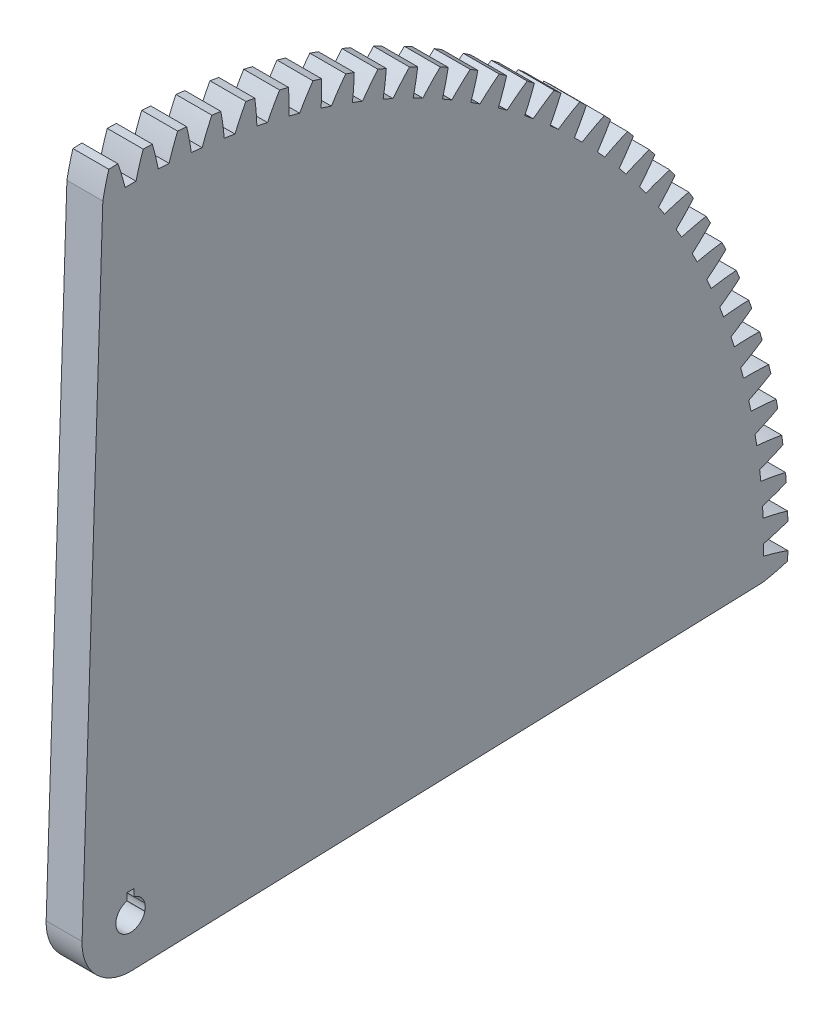
SolidWorks part; units mm, degrees
ref_plane "Plane1" through (0, 0, 0) normal (0, 0, 1) x (1, 0, 0)
ref_plane "Plane2" through (0, 0, 0) normal (0, 1, 0) x (1, 0, 0)
ref_plane "Plane3" through (0, 0, 0) normal (1, 0, 0) x (0, 0, -1)
sketch "HoldingSke" plane through (0, 0, 0) normal (0, 1, 0) x (1, 0, 0)
  line L0 (0, 0) -> (-0.1667, -0.2887)
  line L1 (-15, 0) -> (100, 0) construction
  line L2 (0, 0) -> (-2.1039, 2.3779)
  line L3 (0, 0) -> (-11.863, 4.5341)
  line L4 (0, 0) -> (-4.318, 7.479)
  line L5 (0, 0) -> (-46.8476, -17.4728)
  line L6 (0, 0) -> (-8.2896, -5.593)
  line L7 (-2.1039, 2.3779) -> (8.6586, 51.2059)
  line L8 (-76.2, 54.61) -> (-75.2, 54.61)
  line L9 (-67.7845, 28.3722) -> (-49.3413, 33.142)
  line L10 (-76.2, 71.12) -> (104.1128, 71.12)
  line L11 (0, 0) -> (-10, 0)
  line L12 (-76.2, 101.6) -> (-76.093, 101.6)
  line L13 (24.9733, 27.94) -> (52.9518, 28.4284)
  line L14 (24.9733, 27.94) -> (24.9743, 27.94)
  line L15 (24.9733, 27.94) -> (100.4006, 29.5858)
  line L16 (-63.627, -3) -> (-12.827, -3)
  circle A0 centre (0, 0) radius 3
  circle A1 centre (0, 0) radius 37.5
  circle A2 centre (0, 0) radius 37.5
  circle A3 centre (0, 0) radius 3
  dimension "MHD" = 75
  dimension "Hub_dia" = 75
  dimension "Bore" = 6
  dimension "MBD" = 6
  dimension "Num_teeth" = 120
  dimension "Pitch_radius" = 180.3128
  dimension "Pitch" = 0.3333
  dimension "Width" = 10
  dimension "Overall_len" = 50
  dimension "Show_teeth" = 120
  dimension "Thickness" = 10
  dimension "OAL" = 50.0001
  dimension "T_dim" = 1
  dimension "Ap" = 14.5
  dimension "H" = 19.05
  dimension "Backlash" = 0.107
  dimension "Addendum_fac" = 1
  dimension "Dedendum_fac" = 1.25
  dimension "Clearance_fac" = 0.25
  dimension "Dedendum_add" = 0.001
  dimension "Module" = 3
sketch "BasProSke" plane through (0, 0, 0) normal (0, 1, 0) x (1, 0, 0)
  line L0 (-10, 0) -> (60, 0) construction
  line L1 (0, 0) -> (0, 183)
  line L2 (0, 0) -> (10, 0)
  line L3 (10, 0) -> (10, 183)
  line L4 (10, 183) -> (0, 183)
  dimension "Diameter" = 366
  dimension "Thickness" = 10
revolve "Base-Revolve" add sketch "BasProSke" angle 360 about L0
sketch "TooCutSke" plane through (0, 0, 0) normal (1, 0, 0) x (0, 0, -1)
  line L1 (0, 0) -> (0, 107) construction
  line L2 (0, 0) -> (-2.5434, 179.982) construction
  line L3 (0, 0) -> (-9.423, 359.8505) construction
  line L4 (-2.5434, 179.982) -> (-4.7115, 179.9253) construction
  arc A0 (1.5113, 176.2425) -> (-1.5113, 176.2425) centre (0, 0) ccw
  arc A1 (3.5347, 182.9913) -> (-3.5347, 182.9913) centre (0, 0) ccw
  circle A2 centre (0, 0) radius 180 construction
  circle A3 centre (0, 0) radius 174.2666 construction
  arc A4 (-1.5113, 176.2425) -> (-3.5347, 182.9913) centre (-71.4076, 158.9648) ccw
  arc A5 (3.5347, 182.9913) -> (1.5113, 176.2425) centre (71.4076, 158.9648) ccw
  dimension "Root_dia" = 352.498
  dimension "Overcut_dia" = 366.0508
  dimension "Pitch_dia" = 360
  dimension "Base_dia" = 348.5332
  dimension "Flank_rad" = 72
  dimension "Half_ang" = 1.5
  dimension "Half_CT" = 2.1689
extrude "ToothCut" cut sketch "TooCutSke" along normal through all
fillet "Breaks" [suppressed] radius 0.06
fillet "RootFillets" [suppressed] radius 0.751
pattern_circular "TeethCuts" count 120 every 3 about axis through (-10, 0, 0) along (1, 0, 0) of "ToothCut", "RootFillets", "Breaks"
sketch "HubNeaOneSke" [suppressed] plane through (0, 0, 0) normal (-1, 0, 0) x (0, 0, 1)
  circle A0 centre (0, 0) radius 12.499
  dimension "Diameter" = 75
extrude "HubNearOne" [suppressed] add sketch "HubNeaOneSke" along normal blind 40.0001
sketch "HubNeaBotSke" [suppressed] plane through (0, 0, 0) normal (-1, 0, 0) x (0, 0, 1)
  circle A0 centre (0, 0) radius 12.7
  dimension "Diameter" = 75
extrude "HubNearBoth" [suppressed] add sketch "HubNeaBotSke" along normal blind 20
ref_plane "FarPln" through (10, 0, 0) normal (1, 0, 0) x (0, 0, -1)
sketch "HubFarSke" [suppressed] plane through (12.7, 0, 0) normal (1, 0, 0) x (0, 0, -1)
  circle A0 centre (0, 0) radius 12.7
  dimension "Diameter" = 75
extrude "HubFar" [suppressed] add sketch "HubFarSke" along normal blind 20
sketch "BorSke" plane through (0, 0, 0) normal (1, 0, 0) x (0, 0, -1)
  circle A0 centre (0, 0) radius 3
  dimension "Diameter" = 6
extrude "Bore" cut sketch "BorSke" along normal mid plane 100.0001
sketch "KeySke" plane through (0, 0, 0) normal (1, 0, 0) x (0, 0, -1)
  line L0 (-1, 0) -> (-1, 4)
  line L1 (-1, 4) -> (1, 4)
  line L2 (1, 4) -> (1, 0)
  line L3 (0, 0) -> (0, 34) construction
  line L4 (-1, 0) -> (1, 0)
  dimension "Offset" = 4
  dimension "Width" = 2
extrude "Keyway" cut sketch "KeySke" along normal mid plane 100.0001
pattern_circular "Keyway2" count 2 every 90 about axis through (0, 0, 0) along (1, 0, 0) of "Keyway"
sketch "Sketch1" plane through (10, 0, 0) normal (1, 0, 0) x (0, 0, -1)
  line L0 (0, 224.3134) -> (0, 0) construction
  line L1 (0, 0) -> (213.6921, 0) construction
  line L2 (176.0801, -7.7145) -> (0.4439, -13.4927)
  line L3 (-7.7145, 176.0801) -> (-13.4927, 0.4439)
  line L4 (176.0801, -7.7145) -> (186.3109, -8.4985)
  line L5 (186.3109, -8.4985) -> (187.8056, -54.5918)
  line L6 (187.8056, -54.5918) -> (141.6436, -161.7802)
  line L7 (141.6436, -161.7802) -> (0.4439, -208.078)
  line L8 (0.4439, -208.078) -> (-102.8323, -176.0574)
  line L9 (-102.8323, -176.0574) -> (-161.48, -112.2681)
  line L10 (-161.48, -112.2681) -> (-203.2321, -19.1491)
  line L11 (-203.2321, -19.1491) -> (-189.3957, 62.8481)
  line L12 (-189.3957, 62.8481) -> (-115.067, 184.8791)
  line L13 (-115.067, 184.8791) -> (-32.7498, 211.87)
  line L14 (-32.7498, 211.87) -> (-14.2518, 194.7007)
  line L15 (-14.2518, 194.7007) -> (-7.7145, 176.0801)
  arc A0 (-13.4927, 0.4439) -> (0.4439, -13.4927) centre (0, 0) ccw
  dimension "D1" = 27
extrude "Cut-Extrude1" cut sketch "Sketch1" against normal through all
sketch "Sketch2" plane through (10, 0, 0) normal (1, 0, 0) x (0, 0, -1)
  line L0 (-1, 3.9762) -> (-1, 6)
  line L1 (-1, 4) -> (-1, 2.8284) construction
  line L2 (-1, 6) -> (1, 6)
  line L3 (1, 6) -> (1, 3.9762)
  line L4 (1, 4) -> (-1, 4) construction
  arc A0 (-1, 3.9762) -> (1, 3.9762) centre (0, 0) ccw
  dimension "D1" = 8.2
  dimension "D2" = 2
extrude "Cut-Extrude2" cut sketch "Sketch2" against normal through all
equation "' \"Module@HoldingSke\" = 6.35"
equation "' \"Num_teeth@HoldingSke\" = 12"
equation "' \"Ap@HoldingSke\" =  20"
equation "' \"Width@HoldingSke\" = 0.5 * 25.4"
equation "' \"Hub_dia@HoldingSke\"= 1 * 25.4"
equation "' \"Overall_len@HoldingSke\" = 1.0 * 25.4"
equation "' \"Bore@HoldingSke\" = 0.75 * 25.4"
equation "' \"T_dim@HoldingSke\" = 0.1 * 25.4"
equation "' \"Width@KeySke\" = 0.25 * 25.4"
equation "' \"Show_teeth@HoldingSke\" = 13"
equation "' \"Backlash@HoldingSke\" = 0.009 * 25.4"
equation "' \"Addendum_fac@HoldingSke\" = 1.0"
equation "' \"Dedendum_fac@HoldingSke\" = 1.25"
equation "' \"Dedendum_add@HoldingSke\" = 0.00005 * 25.4"
equation "' \"Clearance_fac@HoldingSke\" = 0.25"
equation "\"Pitch@HoldingSke\" = 1 / \"Module@HoldingSke\""
equation "\"Overcut_dia@TooCutSke\" = (\"Num_teeth@HoldingSke\" + 2 * \"Addendum_fac@HoldingSke\") / \"Pitch@HoldingSke\" + 0.002 * 25.4"
equation "\"Pitch_dia@TooCutSke\" = \"Num_teeth@HoldingSke\" / \"Pitch@HoldingSke\""
equation "\"Base_dia@TooCutSke\" = \"Num_teeth@HoldingSke\" / \"Pitch@HoldingSke\" * cos((\"Ap@HoldingSke\"  * 3.14159265 / 180))"
equation "\"Root_dia@TooCutSke\" = (\"Num_teeth@HoldingSke\" + 2) / \"Pitch@HoldingSke\" - 2 * (\"Addendum_fac@HoldingSke\" + \"Dedendum_fac@HoldingSke\") / \"Pitch@HoldingSke\" - \"Dedendum_add@HoldingSke\" * 2"
equation "\"Half_ang@TooCutSke\" = 180 / \"Num_teeth@HoldingSke\""
equation "\"Half_CT@TooCutSke\" = \"Num_teeth@HoldingSke\" / \"Pitch@HoldingSke\" * sin((3.14159265 / 2 / \"Num_teeth@HoldingSke\")) / 2 - 7 * \"Backlash@HoldingSke\" / 4"
equation "\"Flank_rad@TooCutSke\" = \"Num_teeth@HoldingSke\" / \"Pitch@HoldingSke\" / 5"
equation "\"Radius@RootFillets\" = \"Clearance_fac@HoldingSke\" / \"Pitch@HoldingSke\" + \"Dedendum_add@HoldingSke\""
equation "\"Break_rad@Breaks\" = 0.02 / \"Pitch@HoldingSke\""
equation "\"Thickness@HoldingSke\" = \"Width@HoldingSke\""
equation "\"OAL@HoldingSke\" = \"Thickness@HoldingSke\""
equation "\"MHD@HoldingSke\" = (\"Num_teeth@HoldingSke\" + 2) / \"Pitch@HoldingSke\" - 2 * (\"Addendum_fac@HoldingSke\" + \"Dedendum_fac@HoldingSke\")  / \"Pitch@HoldingSke\" - \"Dedendum_add@HoldingSke\" * 2"
equation "\"MBD@HoldingSke\" = (\"Num_teeth@HoldingSke\" + 2) / \"Pitch@HoldingSke\" - 2 * (\"Addendum_fac@HoldingSke\" + \"Dedendum_fac@HoldingSke\")  / \"Pitch@HoldingSke\" - \"Dedendum_add@HoldingSke\" * 2 - 0.002 * 25.4"
equation "\"MHD@HoldingSke\" = ((sgn( \"MHD@HoldingSke\" - \"Hub_dia@HoldingSke\" )-1)*( \"MHD@HoldingSke\" - \"Hub_dia@HoldingSke\" ))/-2+ \"Hub_dia@HoldingSke\""
equation "\"MBD@HoldingSke\" = ((sgn( \"MBD@HoldingSke\" - \"Bore@HoldingSke\" )-1)*( \"MBD@HoldingSke\" - \"Bore@HoldingSke\" ))/-2+ \"Bore@HoldingSke\""
equation "\"OAL@HoldingSke\" = ((sgn( \"OAL@HoldingSke\" - \"Overall_len@HoldingSke\" )+1)*( \"OAL@HoldingSke\" - \"Overall_len@HoldingSke\" ))/2 + \"Overall_len@HoldingSke\" + 0.000002 * 25.4"
equation "\"Num_teeth@TeethCuts\" = int( \"Show_teeth@HoldingSke\" ) + 1"
equation "\"Num_teeth@TeethCuts\" = ((sgn( \"Num_teeth@TeethCuts\" - \"Num_teeth@HoldingSke\" )-1)*( \"Num_teeth@TeethCuts\" - \"Num_teeth@HoldingSke\" ))/-2+ \"Num_teeth@HoldingSke\""
equation "\"Num_teeth@TeethCuts\" = ((sgn( \"Num_teeth@TeethCuts\" - 2.0)+1)*( \"Num_teeth@TeethCuts\" - 2.0))/2 +2.0"
equation "\"Angle@TeethCuts\" = 360.0 / \"Num_teeth@HoldingSke\""
equation "\"Diameter@BasProSke\" = (\"Num_teeth@HoldingSke\" + 2 * \"Addendum_fac@HoldingSke\") / \"Pitch@HoldingSke\""
equation "\"Thickness@BasProSke\"  = \"Thickness@HoldingSke\""
equation "' \"Fillet_rad@BasProSke\" =  \"Thickness@HoldingSke\" * 0.05"
equation "\"MHD@HoldingSke\" = ((sgn( \"MHD@HoldingSke\" - \"Root_dia@TooCutSke\" )-1)*( \"MHD@HoldingSke\" - \"Root_dia@TooCutSke\" ))/-2+ \"Root_dia@TooCutSke\""
equation "\"Diameter@HubNeaOneSke\" = \"MHD@HoldingSke\""
equation "\"Length@HubNearOne\" = \"OAL@HoldingSke\" - \"Thickness@BasProSke\""
equation "\"Diameter@HubNeaBotSke\" = \"MHD@HoldingSke\""
equation "\"Length@HubNearBoth\" = ( \"OAL@HoldingSke\" - \"Thickness@BasProSke\" ) / 2.0"
equation "\"Thickness@FarPln\" = \"Thickness@BasProSke\""
equation "\"Diameter@HubFarSke\" = \"MHD@HoldingSke\""
equation "\"Length@HubFar\" = ( \"OAL@HoldingSke\" - \"Thickness@BasProSke\" ) / 2.0"
equation "\"Diameter@BorSke\" = \"MBD@HoldingSke\""
equation "\"D1@Bore\" = \"OAL@HoldingSke\" * 2.0"
equation "\"D1@Keyway\" = \"OAL@HoldingSke\" * 2.0"
equation "\"Offset@KeySke\" = \"T_dim@HoldingSke\" + \"MBD@HoldingSke\" / 2.0"
